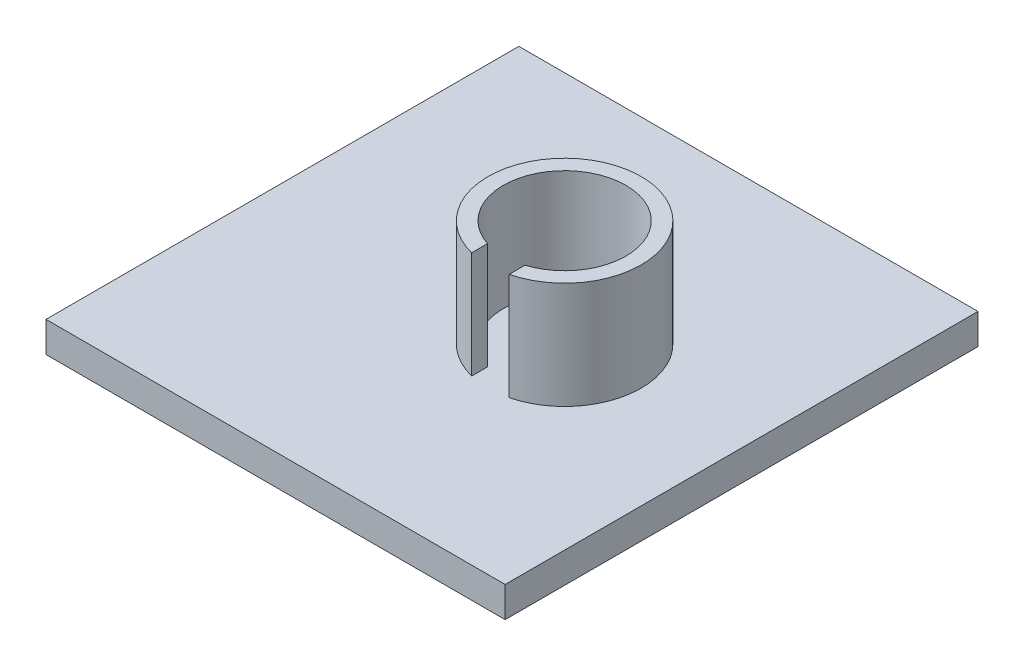
SolidWorks part; units mm, degrees
ref_plane "Front Plane" through (0, 0, 0) normal (0, 0, 1) x (1, 0, 0)
ref_plane "Top Plane" through (0, 0, 0) normal (0, 1, 0) x (1, 0, 0)
ref_plane "Right Plane" through (0, 0, 0) normal (1, 0, 0) x (0, 0, -1)
sketch "Sketch1" plane through (0, 0, 0) normal (0, 1, 0) x (1, 0, 0)
  line L1 (-80, -80) -> (80, -80)
  line L2 (-80, -80) -> (-80, 80)
  line L3 (-80, 80) -> (80, 80)
  line L4 (80, -80) -> (80, 80)
  line L5 (-80, -80) -> (80, 80) construction
  line L6 (-80, 80) -> (80, -80) construction
  point P0 (0, 0)
  dimension "D1" = 160
  dimension "D2" = 160
extrude "Boss-Extrude1" add sketch "Sketch1" along normal mid plane 10
sketch "Sketch3" plane through (0, 5, 0) normal (0, 1, 0) x (1, 0, 0)
  line L1 (80, 80) -> (-80, 80) construction
  line L4 (0, 74) -> (0, 23) construction
  line L6 (-52, 23) -> (-72, 23) construction
  line L7 (0, 80) -> (0, -55)
  line L8 (0, 23) -> (-52, 23) construction
  line L9 (-52, 23) -> (-52, 63.419)
  line L10 (-52, 63.419) -> (-52, -30.581)
  circle A0 centre (0, 23) radius 43.5
  dimension "D5" = 87
  dimension "D4" = 51
  dimension "D7" = 135
  dimension "D8" = 52
  dimension "D9" = 94
  dimension "D10" = 20
sketch "Sketch17" plane through (0, 5, 0) normal (0, 1, 0) x (1, 0, 0)
  line L0 (0, 80) -> (0, -55) construction
  line L1 (0, 23) -> (-52, 23) construction
  line L4 (-6.1352, 3.8592) -> (-6.1352, -1.3386)
  line L5 (6.1352, 3.8592) -> (6.1352, -1.3386)
  arc A0 (6.1352, 3.8592) -> (-6.1352, 3.8592) centre (0, 23) ccw
  arc A1 (6.1352, -1.3386) -> (-6.1352, -1.3386) centre (0, 23) ccw
  dimension "D1" = 40.2
  dimension "D2" = 50.2
  dimension "D4" = 12.2703
extrude "Boss-Extrude8" add sketch "Sketch17" along normal blind 35
sketch "Sketch23" plane through (0, 0, -80) normal (0, 0, -1) x (-1, 0, 0)
  line L1 (-80, 5) -> (80, 5)
  line L2 (-80, 5) -> (-80, -5)
  line L3 (-80, -5) -> (80, -5)
  line L4 (80, 5) -> (80, -5)
extrude "Boss-Extrude12" add sketch "Sketch23" along normal blind 20
sketch "Sketch25" plane through (0, 5, 0) normal (0, 1, 0) x (1, 0, 0)
  line L0 (-80, 100) -> (80, 100) construction
  line L1 (80, -80) -> (58.5, -80)
  line L2 (80, -80) -> (80, 100)
  line L3 (80, 100) -> (58.5, 100)
  line L4 (58.5, -80) -> (58.5, 100)
extrude "Cut-Extrude4" cut sketch "Sketch25" against normal blind 10
sketch "Sketch27" plane through (0, 5, 0) normal (0, 1, 0) x (1, 0, 0)
  line L0 (58.5, 100) -> (58.5, -80) construction
  line L1 (-80, -80) -> (58.5, -80)
  line L2 (-80, -80) -> (-80, -55)
  line L3 (-80, -55) -> (58.5, -55)
  line L4 (58.5, -80) -> (58.5, -55)
  dimension "D1" = 25
extrude "Cut-Extrude5" cut sketch "Sketch27" against normal blind 10
sketch "Sketch28" plane through (0, 5, 0) normal (0, 1, 0) x (1, 0, 0)
  line L1 (-80, -55) -> (-90, -55)
  line L2 (-80, -55) -> (-80, 100)
  line L3 (-80, 100) -> (-90, 100)
  line L4 (-90, -55) -> (-90, 100)
  dimension "D1" = 155
  dimension "D2" = 10
extrude "Boss-Extrude14" add sketch "Sketch28" against normal blind 10
sketch "Sketch34" plane through (0, 5, 0) normal (0, 1, 0) x (1, 0, 0)
  line L0 (-52, -30.581) -> (-52, -53.581) construction
  line L1 (-52, -53.581) -> (-82, -53.581) construction
  line L2 (-82, -30.581) -> (-82, 79.419) construction
  line L3 (-82, -53.581) -> (-22, -53.581)
  line L4 (-82, -53.581) -> (-82, -30.581)
  line L5 (-82, -30.581) -> (-22, -30.581)
  line L6 (-22, -53.581) -> (-22, -30.581)
  line L9 (-82, 79.419) -> (-22, 79.419)
  line L10 (-82, 79.419) -> (-82, 70.419)
  line L11 (-82, 70.419) -> (-22, 70.419)
  line L12 (-22, 79.419) -> (-22, 70.419)
  dimension "D1" = 23
  dimension "D2" = 30
  dimension "D3" = 60
  dimension "D4" = 110
  dimension "D5" = 9
  dimension "D6" = 60
sketch "Sketch37" plane through (0, 5, 0) normal (0, 1, 0) x (1, 0, 0)
  line L0 (58.5, 22.5) -> (48.5, 22.5) construction
  line L1 (58.5, 100) -> (58.5, -55) construction
  line L2 (-22, 70.419) -> (48.5, 70.419) construction
  line L3 (-22, -30.581) -> (48.5, -30.581) construction
  line L4 (48.5, 70.419) -> (48.5, -30.581) construction
  line L5 (48.5, -30.581) -> (48.5, -40.581) construction
  line L6 (48.5, 70.419) -> (48.5, 80.419) construction
  line L7 (48.5, -40.581) -> (-22, -40.581) construction
  line L8 (-22, -53.581) -> (-22, -30.581) construction
  line L9 (-22, -40.581) -> (58.5, -40.581) construction
  dimension "D1" = 10
  dimension "D2" = 10
  dimension "D3" = 101
  dimension "D4" = 70.5
  dimension "D5" = 10
sketch "Sketch39" plane through (0, 5, 0) normal (0, 1, 0) x (1, 0, 0)
  line L0 (-90, 100) -> (-85, 100) construction
  line L1 (-90, 100) -> (58.5, 100) construction
  line L3 (-85, 100) -> (-92, 100)
  line L4 (-85, 100) -> (-85, -55)
  line L5 (-85, -55) -> (-92, -55)
  line L6 (-92, 100) -> (-92, -55)
  dimension "D1" = 5
  dimension "D2" = 155
  dimension "D3" = 7
extrude "Boss-Extrude18" add sketch "Sketch39" against normal blind 10
